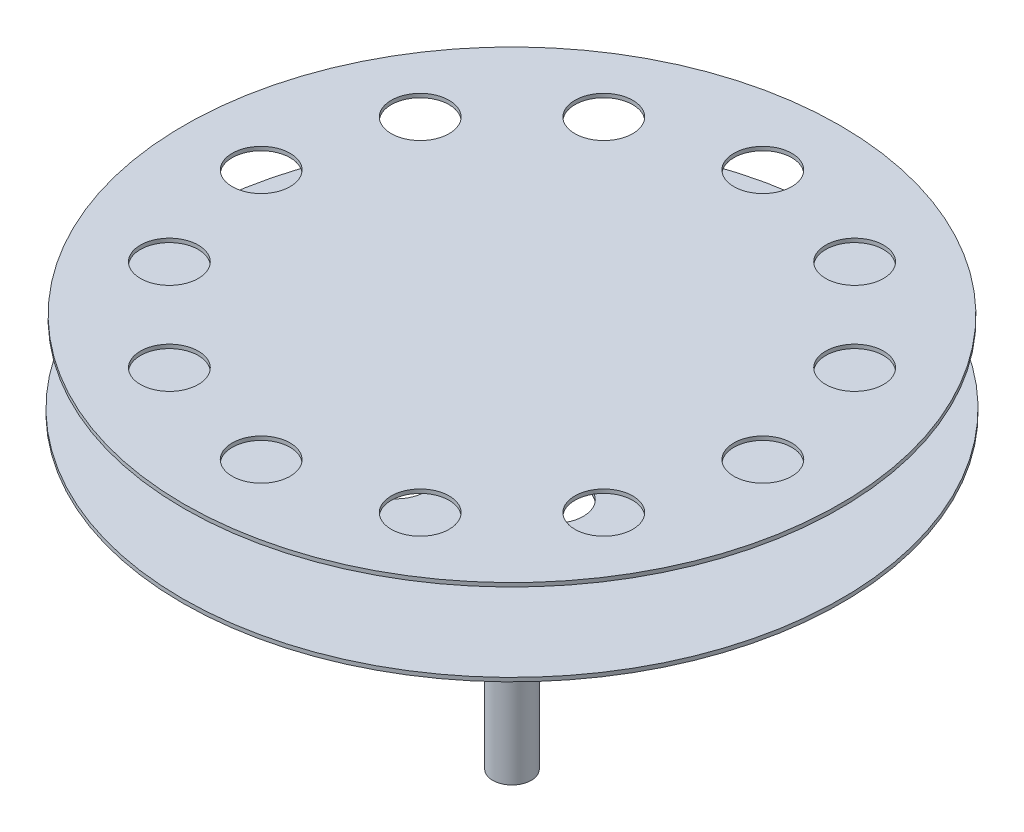
SolidWorks part; units mm, degrees
ref_plane "Front Plane" through (0, 0, 0) normal (0, 0, 1) x (1, 0, 0)
ref_plane "Top Plane" through (0, 0, 0) normal (0, 1, 0) x (1, 0, 0)
ref_plane "Right Plane" through (0, 0, 0) normal (1, 0, 0) x (0, 0, -1)
sketch "Sketch1" plane through (0, 0, 0) normal (0, 0, 1) x (1, 0, 0)
  line L0 (0, 0) -> (0, 52.2611) construction
  line L1 (0, 102) -> (-84.9998, 102)
  line L2 (-84.9998, 102) -> (-84.9998, 101)
  line L3 (-84.9998, 101) -> (-5, 101)
  line L4 (-5, 101) -> (-5, 81)
  line L5 (-5, 81) -> (-85.4031, 81)
  line L6 (-85.4031, 81) -> (-85.4031, 80)
  line L7 (-85.4031, 80) -> (-5, 80)
  line L8 (-5, 80) -> (-5, 0)
  line L9 (-5, 0) -> (0, 0)
  line L10 (0, 0) -> (0, 102)
  line L11 (-5, 81) -> (-5, 80) construction
  dimension "D1" = 84.9998
  dimension "D2" = 1
  dimension "D3" = 20
  dimension "D4" = 5
  dimension "D5" = 80
ref_axis "Axis1" through (0, 54.8742, 0) along (0, -1, 0)
revolve "Revolve1" add sketch "Sketch1" angle 360 about axis through (0, 54.8742, 0) along (0, -1, 0)
sketch "Sketch2" plane through (0, 102, 0) normal (0, 1, 0) x (1, 0, 0)
  line L0 (0, 0) -> (0, 65) construction
  circle A0 centre (0, 65) radius 7.5
  dimension "D1" = 15
  dimension "D2" = 65
extrude "Cut-Extrude1" cut sketch "Sketch2" against normal blind 2
pattern_circular "CirPattern1" count 12 over 360 about axis through (0, 54.8742, 0) along (0, -1, 0) of "Cut-Extrude1"
sketch "Sketch3" plane through (0, 80, 0) normal (0, -1, 0) x (1, 0, 0)
  line L0 (0, 0) -> (0, 30) construction
  circle A0 centre (0, 30) radius 7.5
  dimension "D2" = 15
  dimension "D1" = 30
extrude "Cut-Extrude2" cut sketch "Sketch3" against normal blind 2
pattern_circular "CirPattern2" count 6 over 360 about axis through (0, 54.8742, 0) along (0, -1, 0) of "Cut-Extrude2"
